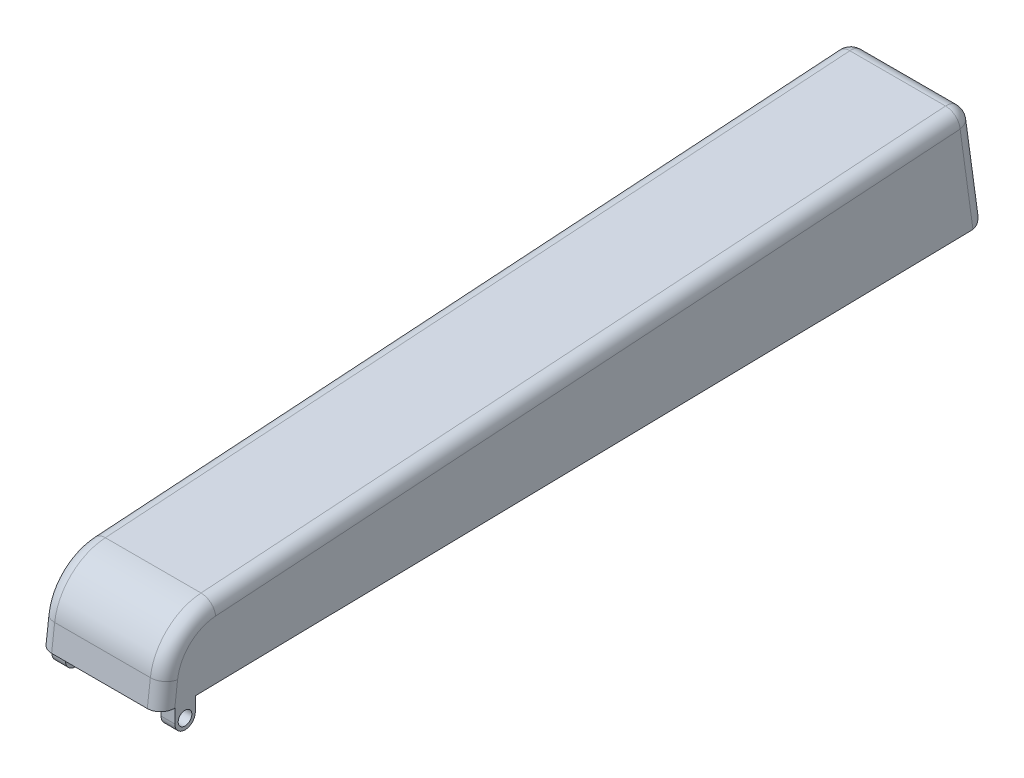
SolidWorks part; units mm, degrees
ref_plane "Front Plane" through (0, 0, 0) normal (0, 0, 1) x (1, 0, 0)
ref_plane "Top Plane" through (0, 0, 0) normal (0, 1, 0) x (1, 0, 0)
ref_plane "Right Plane" through (0, 0, 0) normal (1, 0, 0) x (0, 0, -1)
sketch "Sketch1" plane through (0, 0, 0) normal (1, 0, 0) x (0, 0, -1)
  line L0 (-1631.7716, 0) -> (-1479.3716, 0) construction
  line L1 (-95.3997, -6.5972) -> (58.0227, -3.6151)
  line L2 (58.0227, -3.6151) -> (55.2748, 16.3657)
  line L3 (-95.3997, -6.5972) -> (-94.8346, -1.9067)
  line L4 (-85.4212, 7.0157) -> (55.2748, 16.3657)
  arc A0 (-85.4212, 7.0157) -> (-94.8346, -1.9067) centre (-84.7475, -3.122) ccw
  dimension "D2" = 10.16
  dimension "D1" = 152.4
extrude "Boss-Extrude1" add sketch "Sketch1" along normal blind 22.86
shell "Shell3" thickness 2.54 removed face at (11.43, -5.1062, 18.6885)
sketch "Sketch2" plane through (22.86, 0, 0) normal (1, 0, 0) x (0, 0, -1)
  line L3 (-95.3997, -6.5972) -> (-92.8353, -6.5474) construction
  line L7 (-92.8353, -6.5474) -> (-92.8353, -9.0874) construction
  line L8 (-92.8353, -9.0874) -> (-89.0253, -9.0874) construction
  line L9 (-89.0253, -9.0874) -> (-89.0253, -6.4733) construction
  line L10 (-95.3997, -6.5972) -> (58.0227, -3.6151) construction
  line L11 (-89.0253, -6.4733) -> (-92.8353, -6.5474) construction
  line L12 (-92.8353, -6.5474) -> (-92.8353, -9.0874)
  line L14 (-89.0253, -9.0874) -> (-89.0253, -6.4733)
  line L15 (-89.0253, -6.4733) -> (-92.8353, -6.5474)
  circle A1 centre (-90.9303, -9.0874) radius 1.27
  circle A2 centre (-90.9303, -9.0874) radius 1.905
  line M8 (-95.3997, -6.5972) -> (58.0227, -3.6151)
  dimension "D2" = 2.54
  dimension "D3" = 2.54
  dimension "D1" = 3.81
extrude "Boss-Extrude2" add sketch "Sketch2" against normal blind 2.54 contours M8 | A2 | A1 region at (22.86, -7.1342, 90.9086)
sketch "Sketch5" plane through (0, 10.1022, 0.6713) normal (0, -0.9978, -0.0663) x (-1, 0, 0)
  line L0 (-11.43, 292.9433) -> (-11.43, -177.6328) construction
  point P3 (-11.43, 57.6553)
ref_plane "Plane1" through (11.43, 0, 0) normal (-1, 0, 0) x (0, 0, 1)
mirror "Mirror1" about plane through (11.43, 0, 0) normal (-1, 0, 0) of "Boss-Extrude2"
fillet "Fillet2" radius 2.54 10 edges at (22.86, -4.2519, 95.1171) (22.86, 4.252, 91.7368) (0, -4.2519, 95.1171) (0, 4.252, 91.7368) (11.43, -3.6151, -58.0227) (22.86, 6.3753, -56.6487) (0, 6.3753, -56.6487) (11.43, 16.3657, -55.2748) (22.86, 11.6907, 15.0732) (0, 11.6907, 15.0732)
